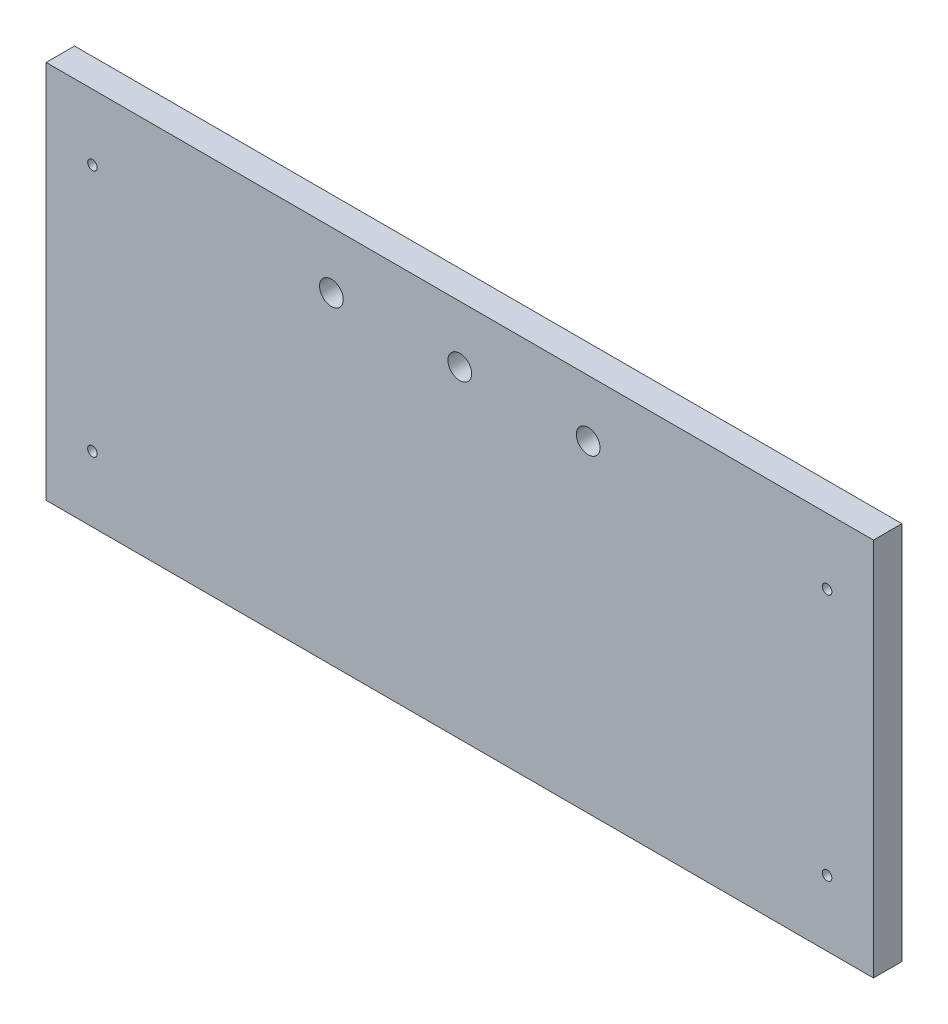
SolidWorks part; units mm, degrees
ref_plane "Front Plane" through (0, 0, 0) normal (0, 0, 1) x (1, 0, 0)
ref_plane "Top Plane" through (0, 0, 0) normal (0, 1, 0) x (1, 0, 0)
ref_plane "Right Plane" through (0, 0, 0) normal (1, 0, 0) x (0, 0, -1)
sketch "Sketch1" plane through (0, 0, 0) normal (0, 0, 1) x (1, 0, 0)
  line L0 (138.525, 127) -> (138.525, 107.95) construction
  line L1 (0, 0) -> (277.05, 0)
  line L2 (0, 0) -> (0, 127)
  line L3 (0, 127) -> (277.05, 127)
  line L4 (277.05, 0) -> (277.05, 127)
  line L5 (9.525, 127) -> (9.525, 0) construction
  line L6 (95.525, 127) -> (95.525, 107.95) construction
  line L7 (267.525, 127) -> (267.525, 0) construction
  line L8 (181.525, 127) -> (181.525, 107.95) construction
  circle A0 centre (95.525, 107.95) radius 3.9687
  circle A1 centre (138.525, 107.95) radius 3.9687
  circle A2 centre (181.525, 107.95) radius 3.9687
  circle A3 centre (15.525, 105) radius 1.6
  circle A4 centre (15.525, 22) radius 1.6
  circle A5 centre (261.525, 105) radius 1.6
  circle A6 centre (261.525, 22) radius 1.6
  dimension "D7" = 7.9375
  dimension "D8" = 7.9375
  dimension "D9" = 7.9375
  dimension "D14" = 3.2
  dimension "D17" = 3.2
  dimension "D19" = 3.2
  dimension "D20" = 3.2
  dimension "D1" = 127
  dimension "D2" = 277.05
  dimension "D3" = 9.525
  dimension "D4" = 86
  dimension "D5" = 9.525
  dimension "D6" = 86
  dimension "D10" = 19.05
  dimension "D11" = 19.05
  dimension "D12" = 19.05
  dimension "D13" = 6
  dimension "D15" = 22
  dimension "D16" = 6
  dimension "D18" = 22
  dimension "D21" = 6
  dimension "D22" = 6
  dimension "D23" = 22
  dimension "D24" = 22
extrude "Boss-Extrude1" add sketch "Sketch1" along normal blind 9.525
equation "\"Length\"= 283mm"
equation "\"Width\"= 225mm"
equation "\"WallThickness\"= 12.5mm"
equation "\"UpperWaterJacketThickness\"= 28mm"
equation "\"SpacerHeight\"= 80.2mm"
equation "\"SpacerCornerWidth\"= 10mm"
equation "\"SpacerCornerHeight\"= 60.16mm"
equation "\"SpacerPegDiameter\"= 10mm"
equation "\"SpacerPegHeight\"= 10mm"
equation "\"TubingShort\"= 110mm"
equation "\"TubingLong\"= 175mm"
equation "\"PlateLength\"= 252mm"
equation "\"PlateWidth\"= 190mm"
equation "\"PlateHoleDiameter\"= 5.9mm"
equation "\"PlateHoleBottom\"= 2mm"
equation "\"PlateHoleSide\"= 1.55mm"
equation "\"PlateHoleSpacing\"= 3.1mm"
equation "\"PlateThickness\"= 1.55mm"
equation "\"ReservoirBottom\"= 12.5mm"
equation "\"ReservoirSupportWidth\"= 12mm"
equation "\"ReservoirSupportHeight\"= 15.1mm"
equation "\"ReservoirSupportPlacementHeight\"= 50mm"
equation "\"ReservoirHoleDiameter\"= 12.7mm"
equation "\"ReservoirHoleRight\"= 25mm"
equation "\"ReservoirHoleTop\"= \"ReservoirSupportPlacementHeight\""
equation "\"ReservoirHeight\"= 90mm"
equation "\"ReservoirPortBottom\"= 4mm"
equation "\"ReservoirPortTop\"= 10mm"
equation "\"ReservoirPortWidth\"= 101mm"
equation "\"CustomSpacerWallThickness\" = 0.375in"
equation "\"CustomSpacerHeight\"= 5in"
equation "\"CustomSpacerRodHoleHeight\"= .75in"
equation "\"CustomSpacerRodHoleDiameter\"= .3125in"
equation "\"ScrewBlockSide\"= 12mm"
equation "\"ScrewBlockUpperHeight\"= 16mm"
equation "\"ScrewBlockLowerHeight\"= 16mm"
equation "\"InternalLength\"= \"Length\" - ( 2 * \"WallThickness\" )"
equation "\"InternalWidth\"= \"Width\" - ( 2 * \"WallThickness\" )"
equation "\"CustomSpacerPegHeight\"= 1in"
equation "\"CustomSpacerScrewBore\"=3.2mm"
equation "\"CustomSpacerScrewDepth\"=10mm"
equation "\"D1@Sketch1\"=\"CustomSpacerHeight\""
equation "\"D2@Sketch1\"=\"InternalLength\"+\"CustomSpacerWallThickness\"*2"
equation "\"D3@Sketch1\"=\"CustomSpacerWallThickness\""
equation "\"D4@Sketch1\"=\"InternalLength\"/3"
equation "\"D5@Sketch1\"=\"CustomSpacerWallThickness\""
equation "\"D6@Sketch1\"=\"InternalLength\"/3"
equation "\"D7@Sketch1\"=\"CustomSpacerRodHoleDiameter\""
equation "\"D8@Sketch1\"=\"CustomSpacerRodHoleDiameter\""
equation "\"D9@Sketch1\"=\"CustomSpacerRodHoleDiameter\""
equation "\"D10@Sketch1\"=\"CustomSpacerRodHoleHeight\""
equation "\"D11@Sketch1\"=\"CustomSpacerRodHoleHeight\""
equation "\"D12@Sketch1\"=\"CustomSpacerRodHoleHeight\""
equation "\"D1@Boss-Extrude1\"=\"CustomSpacerWallThickness\""
equation "\"D13@Sketch1\"=\"ScrewBlockSide\"/2"
equation "\"D14@Sketch1\"=\"CustomSpacerScrewBore\""
equation "\"D15@Sketch1\"=\"ScrewBlockUpperHeight\"+\"ScrewBlockSide\"/2"
equation "\"D16@Sketch1\"=\"ScrewBlockSide\"/2"
equation "\"D17@Sketch1\"=\"CustomSpacerScrewBore\""
equation "\"D18@Sketch1\"=\"ScrewBlockLowerHeight\"+\"ScrewBlockSide\"/2"
equation "\"D19@Sketch1\"=\"CustomSpacerScrewBore\""
equation "\"D20@Sketch1\"=\"CustomSpacerScrewBore\""
equation "\"D21@Sketch1\"=\"ScrewBlockSide\"/2"
equation "\"D22@Sketch1\"=\"ScrewBlockSide\"/2"
equation "\"D23@Sketch1\"=\"ScrewBlockLowerHeight\"+\"ScrewBlockSide\"/2"
equation "\"D24@Sketch1\"=\"ScrewBlockUpperHeight\"+\"ScrewBlockSide\"/2"
